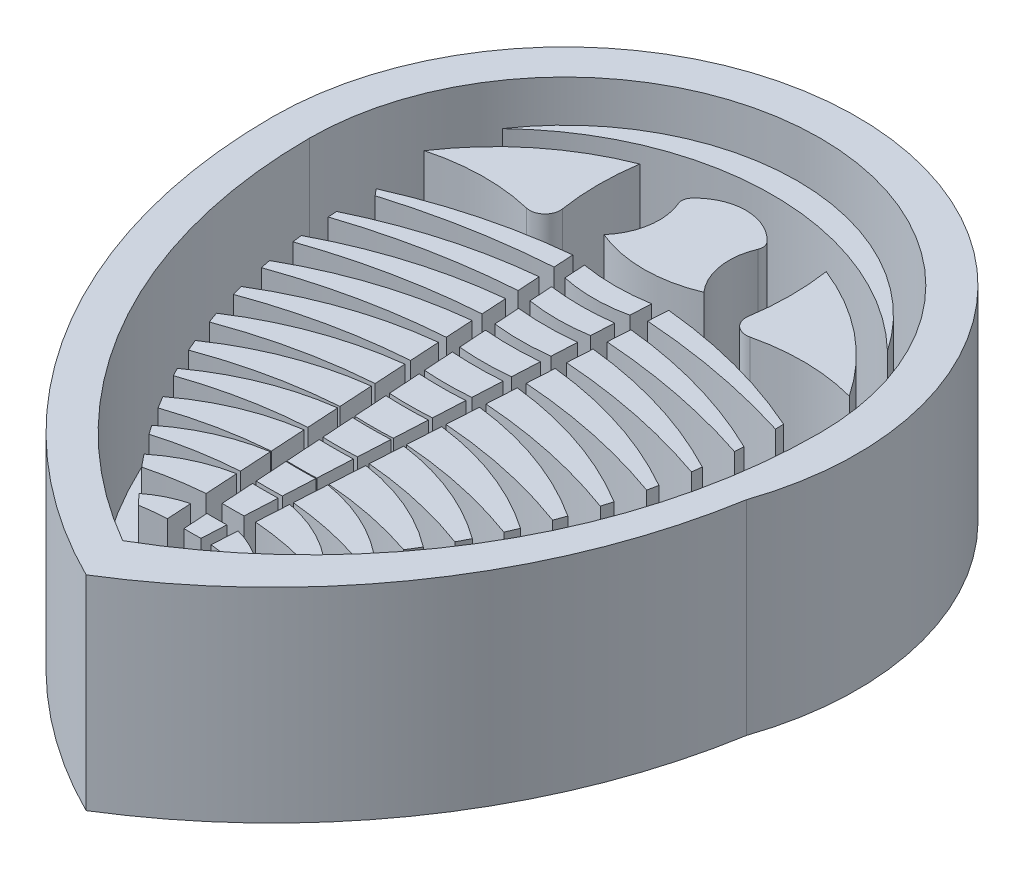
SolidWorks part; units mm, degrees
ref_plane "Přední rovina" through (0, 0, 0) normal (0, 0, 1) x (1, 0, 0)
ref_plane "Horní rovina" through (0, 0, 0) normal (0, 1, 0) x (1, 0, 0)
ref_plane "Pravá rovina" through (0, 0, 0) normal (1, 0, 0) x (0, 0, -1)
sketch "Skica1" plane through (0, 0, 0) normal (0, 1, 0) x (1, 0, 0)
  arc A0 (5, 0) -> (-5, 0) centre (0, 0) ccw
  arc A1 (-5, 0) -> (0, -8.6603) centre (5, 0) ccw
  arc A2 (0, -8.6603) -> (5, 0) centre (-5, 0) ccw
  dimension "D1" = 10
extrude "Přidat vysunutím1" add sketch "Skica1" against normal blind 1
sketch "Skica2" plane through (0, 0, 0) normal (0, 1, 0) x (1, 0, 0)
  line L0 (-0.9396, 1.0946) -> (-0.9163, 0.7054)
  line L1 (0.9396, 1.0946) -> (0.9163, 0.7054)
  line L2 (-0.4639, -6.8657) -> (-0.435, -7.3481)
  line L3 (-0.521, -5.9092) -> (-0.4831, -6.5437)
  line L4 (0.521, -5.9092) -> (0.4831, -6.5437)
  line L5 (-0.5631, -5.2058) -> (-0.5258, -5.8294)
  line L6 (-0.605, -4.5041) -> (-0.5642, -5.1865)
  line L7 (0.605, -4.5041) -> (0.5642, -5.1865)
  line L8 (0.6469, -3.8031) -> (0.6088, -4.4409)
  line L9 (-0.6469, -3.8031) -> (-0.6097, -4.4257)
  line L10 (-0.6887, -3.1028) -> (-0.6498, -3.7549)
  line L11 (0.6887, -3.1028) -> (0.6498, -3.7549)
  line L12 (0.7306, -2.4028) -> (0.6935, -3.0231)
  line L13 (-0.7306, -2.4028) -> (-0.6935, -3.0231)
  line L14 (-0.7724, -1.703) -> (-0.7376, -2.2844)
  line L15 (0.7724, -1.703) -> (0.7376, -2.2844)
  line L16 (0.8142, -1.0034) -> (0.7821, -1.5408)
  line L17 (-0.8142, -1.0034) -> (-0.7821, -1.5408)
  line L18 (-0.856, -0.304) -> (-0.8267, -0.7938)
  line L19 (0.856, -0.304) -> (0.8267, -0.7938)
  line L20 (0.8978, 0.3954) -> (0.8715, -0.0448)
  line L21 (-0.8978, 0.3954) -> (-0.8715, -0.0448)
  line L22 (0.4639, -6.8657) -> (0.434, -7.3648)
  line L23 (0.5631, -5.2058) -> (0.5249, -5.8452)
  line L24 (-0.6539, 1.0367) -> (-0.6272, 0.6279)
  line L25 (0.6621, 1.0381) -> (0.641, 0.6309)
  line L26 (-0.6089, 0.3483) -> (-0.5795, -0.1033)
  line L27 (0.6264, 0.3507) -> (0.6031, -0.0994)
  line L28 (0.5906, -0.3401) -> (0.5649, -0.8356)
  line L29 (-0.5638, -0.3429) -> (-0.5314, -0.8398)
  line L30 (0.5547, -1.0329) -> (0.5266, -1.5735)
  line L31 (-0.5186, -1.0361) -> (-0.4832, -1.5778)
  line L32 (-0.4732, -1.7307) -> (-0.4351, -2.3147)
  line L33 (0.5186, -1.7274) -> (0.4884, -2.3105)
  line L34 (-0.4279, -2.4264) -> (-0.3873, -3.0482)
  line L35 (0.4826, -2.4231) -> (0.4504, -3.0442)
  line L36 (-0.3369, -3.8204) -> (-0.2962, -4.4435)
  line L37 (0.4103, -3.8173) -> (0.378, -4.4401)
  line L38 (0.4464, -3.1197) -> (0.4126, -3.7721)
  line L39 (-0.3824, -3.123) -> (-0.3398, -3.7759)
  line L40 (0.3377, -5.2158) -> (0.3054, -5.8391)
  line L41 (-0.2456, -5.2184) -> (-0.205, -5.8419)
  line L42 (0.374, -4.5159) -> (0.3387, -5.1981)
  line L43 (-0.2913, -4.5188) -> (-0.2468, -5.2012)
  line L44 (-0.1999, -5.9198) -> (-0.1585, -6.554)
  line L45 (0.3013, -5.9174) -> (0.2685, -6.5517)
  line L46 (-0.1376, -6.874) -> (-0.1061, -7.3562)
  line L47 (0.2518, -6.8721) -> (0.2268, -7.3544)
  arc A0 (3.7723, 2.5471) -> (-3.7723, 2.5471) centre (0, 0) ccw
  arc A1 (3.7723, 2.5471) -> (-3.7723, 2.5471) centre (0, -1.3616) ccw
  arc A2 (-1.826, 3.293) -> (-4.1627, 1.4083) centre (0, -1.3616) ccw
  arc A7 (4.1627, 1.4083) -> (2.1882, 1.4375) centre (3.118, -2.4529) ccw
  arc A8 (-1.826, 3.293) -> (-1.8221, 1.7756) centre (3.118, 2.5471) ccw
  arc A9 (4.1627, 1.4083) -> (1.826, 3.293) centre (0, -1.3616) ccw
  arc A10 (1.8221, 1.7756) -> (1.826, 3.293) centre (-3.118, 2.5471) ccw
  arc A11 (-2.1882, 1.4375) -> (-1.8221, 1.7756) centre (-2.1185, 1.7293) ccw
  arc A12 (1.8221, 1.7756) -> (2.1882, 1.4375) centre (2.1185, 1.7293) ccw
  arc A13 (-2.1882, 1.4375) -> (-4.1627, 1.4083) centre (-3.118, -2.4529) ccw
  arc A15 (-0.9784, 1.7445) -> (-0.778, 3.0046) centre (-1.8819, 2.5341) ccw
  arc A16 (0.778, 3.0046) -> (0.9784, 1.7445) centre (1.8819, 2.5341) ccw
  arc A17 (-0.7425, 3.2169) -> (-0.778, 3.0046) centre (-0.594, 3.083) ccw
  arc A18 (0.778, 3.0046) -> (0.7425, 3.2169) centre (0.594, 3.083) ccw
  arc A20 (3.996, 0.288) -> (0.9396, 1.0946) centre (0, -8.6603) ccw
  arc A21 (-0.9784, 1.7445) -> (0.9784, 1.7445) centre (0, 4.0705) ccw
  arc A22 (0.7425, 3.2169) -> (-0.7425, 3.2169) centre (0, 2.5471) ccw
  arc A23 (3.989, -0.4811) -> (0.8978, 0.3954) centre (0, -8.6603) ccw
  arc A24 (3.9271, -1.2348) -> (0.856, -0.304) centre (0, -8.6603) ccw
  arc A25 (3.8134, -1.9708) -> (0.8142, -1.0034) centre (0, -8.6603) ccw
  arc A26 (3.6503, -2.6874) -> (0.7724, -1.703) centre (0, -8.6603) ccw
  arc A27 (3.4403, -3.3825) -> (0.7306, -2.4028) centre (0, -8.6603) ccw
  arc A28 (3.1856, -4.0546) -> (0.6887, -3.1028) centre (0, -8.6603) ccw
  arc A29 (2.8883, -4.702) -> (0.6469, -3.8031) centre (0, -8.6603) ccw
  arc A30 (2.5505, -5.3234) -> (0.605, -4.5041) centre (0, -8.6603) ccw
  arc A31 (2.1739, -5.9172) -> (0.5631, -5.2058) centre (0, -8.6603) ccw
  arc A32 (1.76, -6.4825) -> (0.521, -5.9092) centre (0, -8.6603) ccw
  arc A33 (1.1422, -7.2005) -> (0.4639, -6.8657) centre (0, -8.6603) ccw
  arc A34 (-4.9974, -0.2302) -> (0, -8.6603) centre (5, 0) ccw
  arc A35 (0, -8.6603) -> (4.9974, -0.2302) centre (-5, 0) ccw
  arc A36 (3.9992, 0.1259) -> (0.9163, 0.7054) centre (0, -12.6603) ccw
  arc A37 (3.9794, -0.6572) -> (0.8715, -0.0448) centre (0, -12.6603) ccw
  arc A38 (3.903, -1.4236) -> (0.8267, -0.7938) centre (0, -12.6603) ccw
  arc A39 (3.773, -2.1713) -> (0.7821, -1.5408) centre (0, -12.6603) ccw
  arc A40 (3.5921, -2.8981) -> (0.7376, -2.2844) centre (0, -12.6603) ccw
  arc A41 (3.3628, -3.6022) -> (0.6935, -3.0231) centre (0, -12.6603) ccw
  arc A42 (3.0872, -4.2819) -> (0.6498, -3.7549) centre (0, -12.6603) ccw
  arc A43 (2.7721, -4.9273) -> (0.6088, -4.4409) centre (-0.103, -12.6603) ccw
  arc A44 (2.4059, -5.5618) -> (0.5642, -5.1865) centre (0, -12.6603) ccw
  arc A45 (2.01, -6.1506) -> (0.5249, -5.8452) centre (-0.103, -12.6603) ccw
  arc A46 (1.5622, -6.7269) -> (0.4831, -6.5437) centre (0, -12.6603) ccw
  arc A47 (0.9136, -7.4357) -> (0.434, -7.3648) centre (-0.103, -12.6603) ccw
  arc A51 (0.9136, -7.4357) -> (1.1422, -7.2005) centre (-6.5, 0) ccw
  arc A52 (-0.9396, 1.0946) -> (-3.996, 0.288) centre (0, -8.6603) ccw
  arc A53 (-1.1422, -7.2005) -> (-0.9445, -7.4046) centre (6.5, 0) ccw
  arc A54 (-1.76, -6.4825) -> (-1.5622, -6.7269) centre (6.5, 0) ccw
  arc A55 (-2.1739, -5.9172) -> (-2.0475, -6.0984) centre (6.5, 0) ccw
  arc A56 (-2.5505, -5.3234) -> (-2.4059, -5.5618) centre (6.5, 0) ccw
  arc A57 (-2.8883, -4.702) -> (-2.8049, -4.8651) centre (6.5, 0) ccw
  arc A58 (-3.1856, -4.0546) -> (-3.0872, -4.2819) centre (6.5, 0) ccw
  arc A59 (-3.4403, -3.3825) -> (-3.3628, -3.6022) centre (6.5, 0) ccw
  arc A60 (-3.6503, -2.6874) -> (-3.5921, -2.8981) centre (6.5, 0) ccw
  arc A61 (-3.8134, -1.9708) -> (-3.773, -2.1713) centre (6.5, 0) ccw
  arc A62 (-3.9271, -1.2348) -> (-3.903, -1.4236) centre (6.5, 0) ccw
  arc A63 (-3.989, -0.4811) -> (-3.9794, -0.6572) centre (6.5, 0) ccw
  arc A64 (3.9992, 0.1259) -> (3.996, 0.288) centre (-6.5, 0) ccw
  arc A65 (3.9794, -0.6572) -> (3.989, -0.4811) centre (-6.5, 0) ccw
  arc A66 (3.903, -1.4236) -> (3.9271, -1.2348) centre (-6.5, 0) ccw
  arc A67 (3.773, -2.1713) -> (3.8134, -1.9708) centre (-6.5, 0) ccw
  arc A68 (3.5921, -2.8981) -> (3.6503, -2.6874) centre (-6.5, 0) ccw
  arc A69 (3.3628, -3.6022) -> (3.4403, -3.3825) centre (-6.5, 0) ccw
  arc A70 (3.0872, -4.2819) -> (3.1856, -4.0546) centre (-6.5, 0) ccw
  arc A71 (2.7721, -4.9273) -> (2.8883, -4.702) centre (-6.5, 0) ccw
  arc A72 (2.4059, -5.5618) -> (2.5505, -5.3234) centre (-6.5, 0) ccw
  arc A73 (2.01, -6.1506) -> (2.1739, -5.9172) centre (-6.5, 0) ccw
  arc A74 (1.5622, -6.7269) -> (1.76, -6.4825) centre (-6.5, 0) ccw
  arc A75 (-0.9163, 0.7054) -> (-3.9992, 0.1259) centre (0, -12.6603) ccw
  arc A76 (-0.8978, 0.3954) -> (-3.989, -0.4811) centre (0, -8.6603) ccw
  arc A77 (-0.8715, -0.0448) -> (-3.9794, -0.6572) centre (0, -12.6603) ccw
  arc A78 (-0.856, -0.304) -> (-3.9271, -1.2348) centre (0, -8.6603) ccw
  arc A79 (-0.8267, -0.7938) -> (-3.903, -1.4236) centre (0, -12.6603) ccw
  arc A80 (-0.8142, -1.0034) -> (-3.8134, -1.9708) centre (0, -8.6603) ccw
  arc A81 (-0.7821, -1.5408) -> (-3.773, -2.1713) centre (0, -12.6603) ccw
  arc A82 (-0.7724, -1.703) -> (-3.6503, -2.6874) centre (0, -8.6603) ccw
  arc A83 (-0.7376, -2.2844) -> (-3.5921, -2.8981) centre (0, -12.6603) ccw
  arc A84 (-0.7306, -2.4028) -> (-3.4403, -3.3825) centre (0, -8.6603) ccw
  arc A85 (-0.6935, -3.0231) -> (-3.3628, -3.6022) centre (0, -12.6603) ccw
  arc A86 (-0.6887, -3.1028) -> (-3.1856, -4.0546) centre (0, -8.6603) ccw
  arc A87 (-0.6498, -3.7549) -> (-3.0872, -4.2819) centre (0, -12.6603) ccw
  arc A88 (-0.6469, -3.8031) -> (-2.8883, -4.702) centre (0, -8.6603) ccw
  arc A89 (-0.6097, -4.4257) -> (-2.8049, -4.8651) centre (-0.103, -12.6603) ccw
  arc A90 (-0.605, -4.5041) -> (-2.5505, -5.3234) centre (0, -8.6603) ccw
  arc A91 (-0.5642, -5.1865) -> (-2.4059, -5.5618) centre (0, -12.6603) ccw
  arc A92 (-0.5631, -5.2058) -> (-2.1739, -5.9172) centre (0, -8.6603) ccw
  arc A93 (-0.5258, -5.8294) -> (-2.0475, -6.0984) centre (-0.103, -12.6603) ccw
  arc A94 (-0.521, -5.9092) -> (-1.76, -6.4825) centre (0, -8.6603) ccw
  arc A95 (-0.4831, -6.5437) -> (-1.5622, -6.7269) centre (0, -12.6603) ccw
  arc A96 (-0.4639, -6.8657) -> (-1.1422, -7.2005) centre (0, -8.6603) ccw
  arc A97 (-0.435, -7.3481) -> (-0.9445, -7.4046) centre (-0.103, -12.6603) ccw
  arc A98 (-3.996, 0.288) -> (-3.9992, 0.1259) centre (6.5, 0) ccw
  arc A100 (5, 0) -> (-5, 0) centre (0, 0) ccw construction
  arc A108 (-0.2913, -4.5188) -> (0.374, -4.5159) centre (0, 5) ccw
  arc A111 (-0.1376, -6.874) -> (0.2518, -6.8721) centre (0, 5) ccw
  arc A112 (-0.6539, 1.0367) -> (0.6621, 1.0381) centre (0, 5) ccw
  arc A113 (-0.5186, -1.0361) -> (0.5547, -1.0329) centre (0, 5) ccw
  arc A114 (-0.4732, -1.7307) -> (0.5186, -1.7274) centre (0, 5) ccw
  arc A115 (-0.5795, -0.1033) -> (0.6031, -0.0994) centre (0, 3.5471) ccw
  arc A116 (-0.6089, 0.3483) -> (0.6264, 0.3507) centre (0, 5) ccw
  arc A117 (-0.5638, -0.3429) -> (0.5906, -0.3401) centre (0, 5) ccw
  arc A118 (-0.4279, -2.4264) -> (0.4826, -2.4231) centre (0, 5) ccw
  arc A119 (-0.4351, -2.3147) -> (0.4884, -2.3105) centre (0, 3.5471) ccw
  arc A120 (-0.3873, -3.0482) -> (0.4504, -3.0442) centre (0, 3.5471) ccw
  arc A121 (-0.3824, -3.123) -> (0.4464, -3.1197) centre (0, 5) ccw
  arc A122 (-0.3369, -3.8204) -> (0.4103, -3.8173) centre (0, 5) ccw
  arc A123 (-0.1999, -5.9198) -> (0.3013, -5.9174) centre (0, 5) ccw
  arc A124 (-0.2456, -5.2184) -> (0.3377, -5.2158) centre (0, 5) ccw
  arc A125 (-0.1585, -6.554) -> (0.2685, -6.5517) centre (0, 3.5471) ccw
  arc A129 (-3.9876, 0.2918) -> (-3.8789, 0.163) centre (0, 3.5471) ccw
  arc A134 (-0.2468, -5.2012) -> (0.3387, -5.1981) centre (0, 3.5471) ccw
  arc A138 (-0.6272, 0.6279) -> (0.641, 0.6309) centre (0, 3.5471) ccw
  arc A139 (-0.4832, -1.5778) -> (0.5266, -1.5735) centre (0, 3.5471) ccw
  arc A140 (-0.2962, -4.4435) -> (0.378, -4.4401) centre (0, 3.5471) ccw
  arc A141 (-0.5314, -0.8398) -> (0.5649, -0.8356) centre (0, 3.5471) ccw
  arc A142 (-0.3398, -3.7759) -> (0.4126, -3.7721) centre (0, 3.5471) ccw
  arc A143 (-0.205, -5.8419) -> (0.3054, -5.8391) centre (0, 3.5471) ccw
  arc A144 (-0.1061, -7.3562) -> (0.2268, -7.3544) centre (0, 3.5471) ccw
  point P44 (0, -12.6603)
  dimension "D1" = 4
  dimension "D4" = 1.5
  dimension "D5" = 1.5
extrude "Přidat vysunutím2" add sketch "Skica2" along normal blind 2.5 contours A97 L2 A96 A53 | A95 L3 A94 A54 | A93 L5 A92 A55 | A91 L6 A90 A56 | A89 L9 A88 A57 | A87 L10 A86 A58 | A85 L13 A84 A59 | A83 L14 A82 A60 | A81 L17 A80 A61 | A77 L21 A76 A63 | A52 A129 A75 L0 | A13 A11 A8 A2 | A1 A0 | A18 A22 A17 A15 A21 A16 | A10 A12 A7 A9 | L24 A138 L25 A112 | A116 L26 A115 L27 | L29 A141 L28 A117 | L31 A139 L30 A113 | L32 A119 L33 A114 | L34 A120 L35 A118 | L39 A142 L38 A121 | L36 A140 L37 A122 | L43 A134 L42 A108 | L41 A143 L40 A124 | L44 A125 L45 A123 | L46 A144 L47 A111 | A47 A51 A33 L22 | A46 A74 A32 L4 | A45 A73 A31 L23 | A44 A72 A30 L7 | A43 A71 A29 L8 | A42 A70 A28 L11 | A41 A69 A27 L12 | A40 A68 A26 L15 | A39 A67 A25 L16 | A38 A66 A24 L19 | A37 A65 A23 L20 | A84 A59 A85 L13 | A78 A62 A79 L18 | A36 L1 A20 A64 region at (-2.2521, 0, -0.6787) region at (-0.7289, 0, 7.169) region at (-1.0328, 0, 6.351) region at (1.0328, 0, 6.351) region at (-1.2291, 0, 5.6712) region at (-1.4297, 0, 5.0378) region at (1.4297, 0, 5.0378) region at (1.6079, 0, 4.3464) region at (-1.5774, 0, 4.3173) region at (-1.7578, 0, 3.6642) region at (1.7578, 0, 3.6642) region at (1.8946, 0, 2.9605) region at (-1.8946, 0, 2.9605) region at (-2.0121, 0, 2.2477) region at (2.0121, 0, 2.2477) region at (2.1095, 0, 1.527) region at (-2.1095, 0, 1.527) region at (2.1859, 0, 0.7993) region at (2.2402, 0, 0.0656) region at (-2.2402, 0, 0.0656) region at (0.728, 0, 7.1802) region at (1.2436, 0, 5.6936) region at (0.0053, 0, -0.7937) region at (0.0101, 0, -0.0961) region at (0.0149, 0, 0.6092) region at (0.0198, 0, 1.3186) region at (0.0246, 0, 2.0295) region at (0.0294, 0, 2.7402) region at (0.0387, 0, 4.13) region at (0.0341, 0, 3.4492) region at (0.0481, 0, 5.5244) region at (0.0436, 0, 4.8548) region at (0.0528, 0, 6.229) region at (0.0587, 0, 7.1089) region at (0, 0, -4.1486) region at (-2.6742, 0, -2.1513) region at (2.6742, 0, -2.1513) region at (0, 0, -2.4956)
ref_plane "Rovina1" through (0, -1, 0) normal (0, -1, 0) x (-1, 0, 0)
sketch "Sketch1" plane through (0, -1, 0) normal (0, -1, 0) x (1, 0, 0)
  arc A0 (-5, 0) -> (5, 0) centre (0, 0) ccw construction
  arc A1 (0, 8.6603) -> (-5, 0) centre (5, 0) ccw construction
  arc A3 (-5, 0) -> (5, 0) centre (0, 0) ccw
  arc A4 (0, 8.6603) -> (-5, 0) centre (5, 0) ccw
  arc A6 (-5.7225, 0) -> (5.4144, 1.8523) centre (0, 0) ccw
  arc A7 (0.2212, 9.5986) -> (-5.7225, 0) centre (5, 0) ccw
  arc A8 (5.4144, 1.8523) -> (0.2212, 9.5986) centre (-5.7225, 0) ccw
  point P5 (5.5674, 0)
  point P7 (0, 9.23)
  point P8 (-5.7225, 0)
  arc M5 (5, 0) -> (0, 8.6603) centre (-5, 0) ccw
  arc M6 (0, 8.6603) -> (-5, 0) centre (5, 0) ccw
  arc M7 (-5, 0) -> (5, 0) centre (0, 0) ccw
extrude "Boss-Extrude1" add sketch "Sketch1" against normal blind 4 contours A6 A8 A7 M5 M7 M6 region at (-3.9537, -1, 5.5442)
